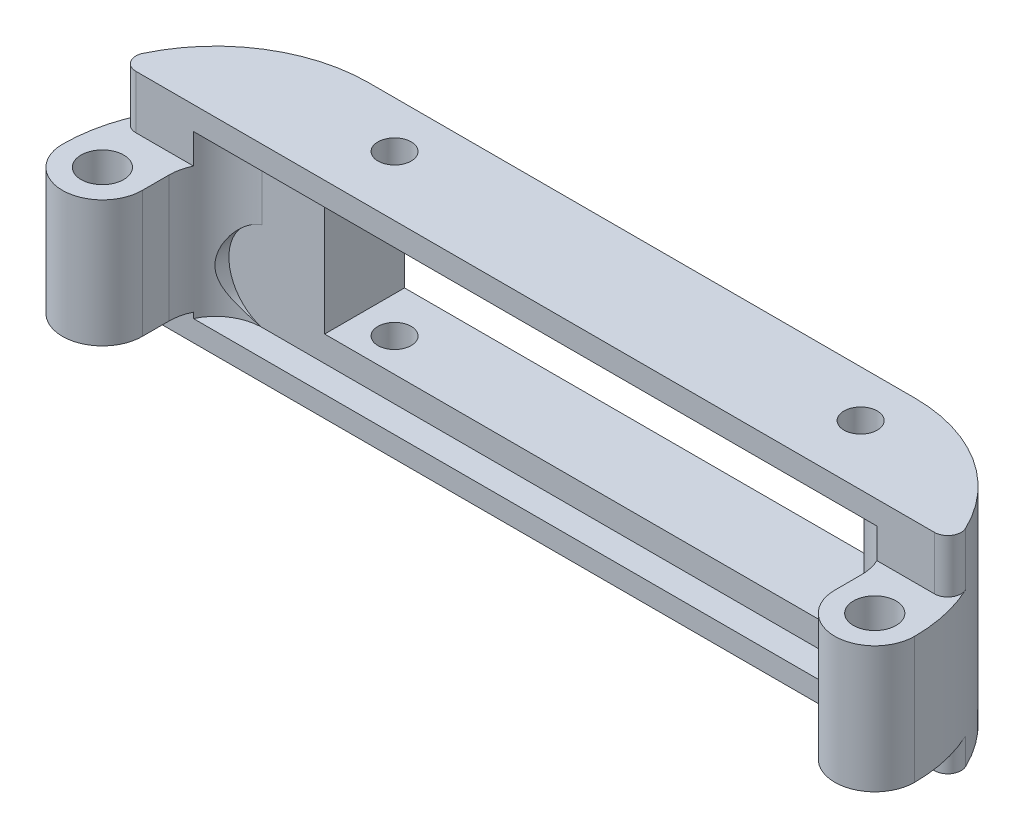
SolidWorks part; units mm, degrees
ref_plane "Plan de face" through (0, 0, 0) normal (0, 0, 1) x (1, 0, 0)
ref_plane "Plan de dessus" through (0, 0, 0) normal (0, 1, 0) x (1, 0, 0)
ref_plane "Plan de droite" through (0, 0, 0) normal (1, 0, 0) x (0, 0, -1)
sketch "Esquisse1" plane through (0, 0, 0) normal (0, 1, 0) x (1, 0, 0)
  line L0 (-29, 0) -> (29, 0) construction
  line L1 (-22.5, 5.5) -> (22.5, 5.5)
  line L2 (-20.5, 11.5) -> (20.5, 11.5)
  line L3 (-26, 0) -> (-26, 2)
  line L5 (26, 2) -> (26, 0)
  circle A0 centre (-29, 0) radius 1.6
  circle A1 centre (29, 0) radius 1.6
  arc A2 (-32, 0) -> (-26, 0) centre (-29, 0) ccw
  arc A3 (26, 0) -> (32, 0) centre (29, 0) ccw
  arc A4 (-20.5, 11.5) -> (-32, 0) centre (-20.5, 0) ccw
  arc A6 (20.5, 11.5) -> (32, 0) centre (20.5, 0) cw
  circle A8 centre (-29, 0) radius 3 construction
  circle A9 centre (29, 0) radius 3 construction
  arc A10 (-22.5, 5.5) -> (-26, 2) centre (-22.5, 2) ccw
  arc A11 (22.5, 5.5) -> (26, 2) centre (22.5, 2) cw
  point P4 (0, 0)
  point P13 (0, 5.5)
  point P16 (0, 11.5)
  dimension "D2" = 3.2
  dimension "D3" = 3
  dimension "D1" = 58
  dimension "D4" = 5.5
  dimension "D5" = 6
  dimension "D6" = 2
extrude "Boss.-Extru.1" add sketch "Esquisse1" along normal blind 15.5
sketch "Esquisse2" plane through (0, 15.5, 0) normal (0, 1, 0) x (1, 0, 0)
  line L1 (-49.4693, -13.8117) -> (39.2144, -13.8117)
  line L2 (-49.4693, -13.8117) -> (-49.4693, 3.5)
  line L3 (-49.4693, 3.5) -> (39.2144, 3.5)
  line L4 (39.2144, -13.8117) -> (39.2144, 3.5)
  dimension "D1" = 3.5
extrude "Enlèv. mat.-Extru.1" cut sketch "Esquisse2" against normal blind 4
extrude "Enlèv. mat.-Extru.2" cut sketch "Esquisse2<2>" along normal blind 2 from surface starting at face at (0, 0, -3.8213)
sketch "Esquisse2<2>" plane through (0, 15.5, 0) normal (0, 1, 0) x (1, 0, 0) same geometry as "Esquisse2"
sketch "Esquisse3" plane through (0, 0, -11.5) normal (0, 0, -1) x (-1, 0, 0)
  line L0 (-22.6906, 3.5) -> (17.8094, 13.75) construction
  line L1 (-22.6906, 13.75) -> (17.8094, 13.75)
  line L2 (-22.6906, 13.75) -> (-22.6906, 3.5)
  line L3 (-22.6906, 3.5) -> (17.8094, 3.5)
  line L4 (17.8094, 13.75) -> (17.8094, 3.5)
  line L5 (-25.6623, 2) -> (-31.4545, 2) construction
  line L6 (-20.5, 15.5) -> (20.5, 0) construction
  point P6 (-22.6906, 13.75)
  dimension "D1" = 40.5
  dimension "D2" = 10.25
  dimension "D3" = 1.5
extrude "Enlèv. mat.-Extru.3" cut sketch "Esquisse3" against normal through all
sketch "Esquisse4" plane through (0, 15.5, 0) normal (0, 1, 0) x (1, 0, 0)
  line L0 (19.9406, 8) -> (-15.0594, 8) construction
  line L3 (-22.5, 5.5) -> (22.5, 5.5) construction
  circle A0 centre (19.9406, 8) radius 1.25
  circle A1 centre (-15.0594, 8) radius 1.25
  dimension "D2" = 2.5
  dimension "D1" = 35
  dimension "D3" = 2.5
  dimension "D4" = 2.75
extrude "Enlèv. mat.-Extru.4" cut sketch "Esquisse4" against normal through all
ref_plane "Plan1" through (29, 0, 0) normal (1, 0, 0) x (0, 0, -1)
ref_plane "Plan2" through (-29, 0, 0) normal (1, 0, 0) x (0, 0, -1)
sketch "Esquisse5" plane through (0, 0, -5.5) normal (0, 0, 1) x (1, 0, 0)
  line L0 (13.3515, 3.58) -> (24, 3.58) construction
  line L5 (-29, -7.425) -> (-29, 7.425) construction
  line L9 (13.3515, 5.58) -> (24, 5.58)
  line L10 (13.3515, 1.58) -> (24, 1.58)
  line L12 (26, 11.5) -> (26, 2) construction
  circle A0 centre (-21.5, 4.9) radius 3.5
  arc A3 (13.3515, 5.58) -> (13.3515, 1.58) centre (13.3515, 3.58) ccw
  arc A4 (24, 1.58) -> (24, 5.58) centre (24, 3.58) ccw
  point P4 (18.6757, 3.58)
  point P17 (13.3515, 5.08)
  dimension "D1" = 7
  dimension "D2" = 7.5
  dimension "D3" = 2.9
  dimension "D4" = 4
  dimension "D5" = 1.58
extrude "Enlèv. mat.-Extru.5" cut sketch "Esquisse5" along normal through all
sketch "Esquisse6" plane through (0, 15.5, 0) normal (0, 1, 0) x (1, 0, 0)
  line L0 (-22.5, 5.5) -> (22.5, 5.5) construction
  line L1 (-22.5, 5.5) -> (22.5, 5.5)
  line L2 (25.6623, 3.5) -> (-25.6623, 3.5)
  arc A0 (-22.5, 5.5) -> (-25.6623, 3.5) centre (-22.5, 2) ccw construction
  arc A1 (25.6623, 3.5) -> (22.5, 5.5) centre (22.5, 2) ccw construction
  arc A2 (-22.5, 5.5) -> (-25.6623, 3.5) centre (-22.5, 2) ccw
  arc A3 (25.6623, 3.5) -> (22.5, 5.5) centre (22.5, 2) ccw
extrude "Boss.-Extru.2" add sketch "Esquisse6" against normal up to surface (1.75 mm away) up to face at (18.6906, 13.75, -8)
extrude "Boss.-Extru.3" add sketch "Esquisse6<2>" along normal up to surface (-13.92 mm away) from surface up to face at (23.5063, 1.58, -5.4152) starting at face at (19.9406, 0, -6.75)
sketch "Esquisse6<2>" plane through (0, 15.5, 0) normal (0, 1, 0) x (1, 0, 0) same geometry as "Esquisse6"
fillet "Congé1" radius 1 4 edges at (31.4545, 1, -3.5) (31.4545, 13.5, -3.5) (-31.4545, 1, -3.5) (-31.4545, 13.5, -3.5)
